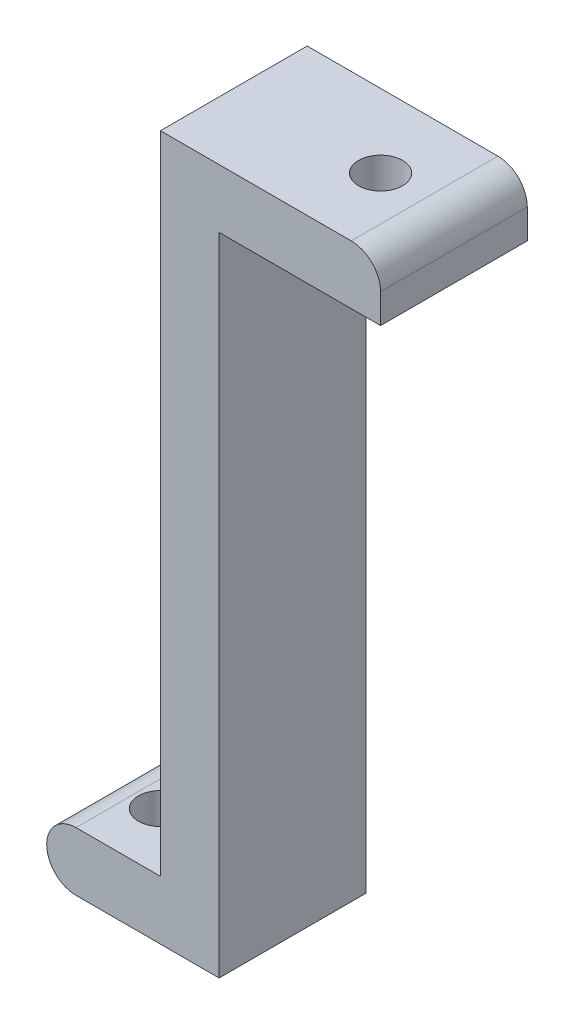
SolidWorks part; units mm, degrees
ref_plane "Front Plane" through (0, 0, 0) normal (0, 0, 1) x (1, 0, 0)
ref_plane "Top Plane" through (0, 0, 0) normal (0, 1, 0) x (1, 0, 0)
ref_plane "Right Plane" through (0, 0, 0) normal (1, 0, 0) x (0, 0, -1)
sketch "Sketch1" plane through (0, 0, 0) normal (0, 0, 1) x (1, 0, 0)
  line L0 (0, 0) -> (-15, 0)
  line L1 (-15, 0) -> (-15, -44)
  line L2 (-15, -44) -> (-22.75, -44)
  line L3 (-22.75, -44) -> (-22.75, -48)
  line L4 (-22.75, -48) -> (-11, -48)
  line L5 (-11, -48) -> (-11, -4)
  line L6 (-11, -4) -> (0, -4)
  line L7 (0, -4) -> (0, 0)
  dimension "D1" = 4
  dimension "D2" = 4
  dimension "D3" = 4
  dimension "D4" = 44
  dimension "D5" = 11.75
  dimension "D6" = 11
extrude "Boss-Extrude1" add sketch "Sketch1" along normal blind 10
sketch "Sketch2" plane through (0, -44, 0) normal (0, 1, 0) x (1, 0, 0)
  line L0 (-22.75, -10) -> (-22.75, 0) construction
  circle A0 centre (-19, -6) radius 1.5
  point P4 (-22.75, -5)
  dimension "D1" = 3
  dimension "D2" = 3.75
  dimension "D3" = 1
extrude "Cut-Extrude1" cut sketch "Sketch2" against normal blind 10
sketch "Sketch3" plane through (0, -4, 0) normal (0, -1, 0) x (-1, 0, 0)
  line L0 (0, -10) -> (0, 0) construction
  circle A0 centre (5, -5) radius 1.5
  point P4 (0, -5)
  dimension "D1" = 3
  dimension "D2" = 0
  dimension "D3" = 5
extrude "Cut-Extrude2" cut sketch "Sketch3" against normal blind 10
fillet "Fillet1" radius 2 1 edges at (0, 0, 5)
fillet "Fillet2" radius 2 2 edges at (-22.75, -48, 5) (-22.75, -44, 5)
